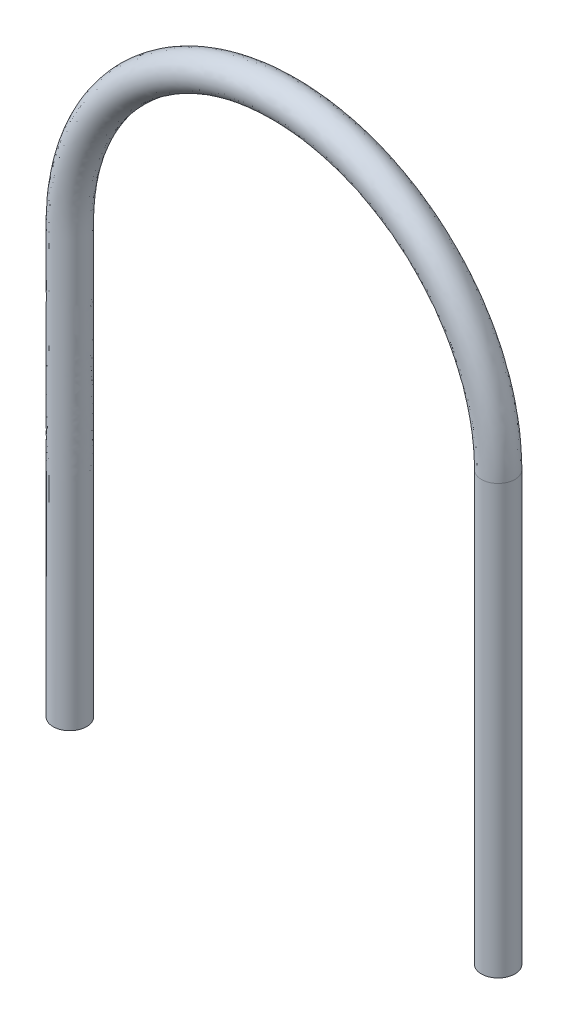
SolidWorks part; units mm, degrees
material "A-Glass Fiber"
ref_plane "Front" through (0, 0, 0) normal (0, 0, 1) x (1, 0, 0)
ref_plane "Top" through (0, 0, 0) normal (0, 1, 0) x (1, 0, 0)
ref_plane "Right" through (0, 0, 0) normal (1, 0, 0) x (0, 0, -1)
sketch "Sketch1" plane through (0, 0, 0) normal (0, 0, 1) x (1, 0, 0)
  line L2 (0, 0) -> (0, -323.85)
  line L4 (323.85, 0) -> (323.85, -323.85)
  arc A0 (0, 0) -> (323.85, 0) centre (161.925, 0) cw
  dimension "D1" = 323.85
  dimension "D2" = 323.85
sketch "Sketch2" plane through (0, 0, 0) normal (0, 1, 0) x (1, 0, 0)
  circle A0 centre (0, 0) radius 12.7
  dimension "D1" = 25.4
sweep "Sweep2" add profiles "Sketch2" path "Sketch1"
sketch "Sketch3" plane through (0, 0, 0) normal (0, 1, 0) x (1, 0, 0)
  circle A0 centre (0, 0) radius 9.525
  dimension "D1" = 19.05
sweep "Cut-Sweep1" cut profiles "Sketch3" path "Sketch1<6>"
sketch "Sketch1<6>" plane through (0, 0, 0) normal (0, 0, 1) x (1, 0, 0) same geometry as "Sketch1"
